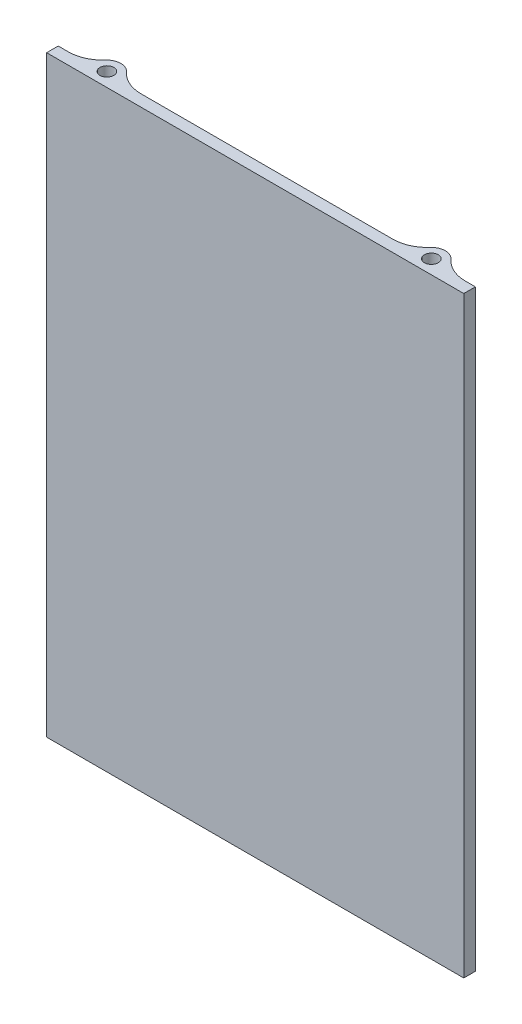
SolidWorks part; units mm, degrees
material "PLA"
ref_plane "Front Plane" through (0, 0, 0) normal (0, 0, 1) x (1, 0, 0)
ref_plane "Top Plane" through (0, 0, 0) normal (0, 1, 0) x (1, 0, 0)
ref_plane "Right Plane" through (0, 0, 0) normal (1, 0, 0) x (0, 0, -1)
other "Center of Mass"
sketch "Sketch1" plane through (0, 0, 0) normal (0, 1, 0) x (1, 0, 0)
  line L8 (90, 5.5) -> (90, 0.5)
  line L9 (90, 5.5) -> (85.6525, 5.5)
  line L15 (90, 0.5) -> (-90, 0.5)
  line L17 (-90, 5.5) -> (-90, 0.5)
  line L19 (90, 5.5) -> (-90, 0.5) construction
  line L20 (90, 0.5) -> (-90, 5.5) construction
  line L21 (-85.6525, 5.5) -> (-90, 5.5)
  line L22 (0, 5.5) -> (0, 0.5) construction
  line L23 (54.3475, 5.5) -> (-54.3475, 5.5)
  circle A19 centre (-70, 6.5) radius 3
  arc A21 (-85.6525, 5.5) -> (-74.4721, 10.5) centre (-85.6525, 20.5) ccw
  arc A22 (-65.5279, 10.5) -> (-54.3475, 5.5) centre (-54.3475, 20.5) ccw
  arc A23 (-65.5279, 10.5) -> (-74.4721, 10.5) centre (-70, 6.5) ccw
  arc A24 (65.5279, 10.5) -> (74.4721, 10.5) centre (70, 6.5) cw
  arc A25 (65.5279, 10.5) -> (54.3475, 5.5) centre (54.3475, 20.5) cw
  arc A26 (85.6525, 5.5) -> (74.4721, 10.5) centre (85.6525, 20.5) cw
  circle A27 centre (70, 6.5) radius 3
  point P1 (0, 3)
  dimension "D3" = 6
  dimension "D4" = 6
  dimension "D6" = 30
  dimension "D1" = 5
  dimension "D2" = 180
  dimension "D7" = 70
extrude "Boss-Extrude1" add sketch "Sketch1" along normal blind 255.8
